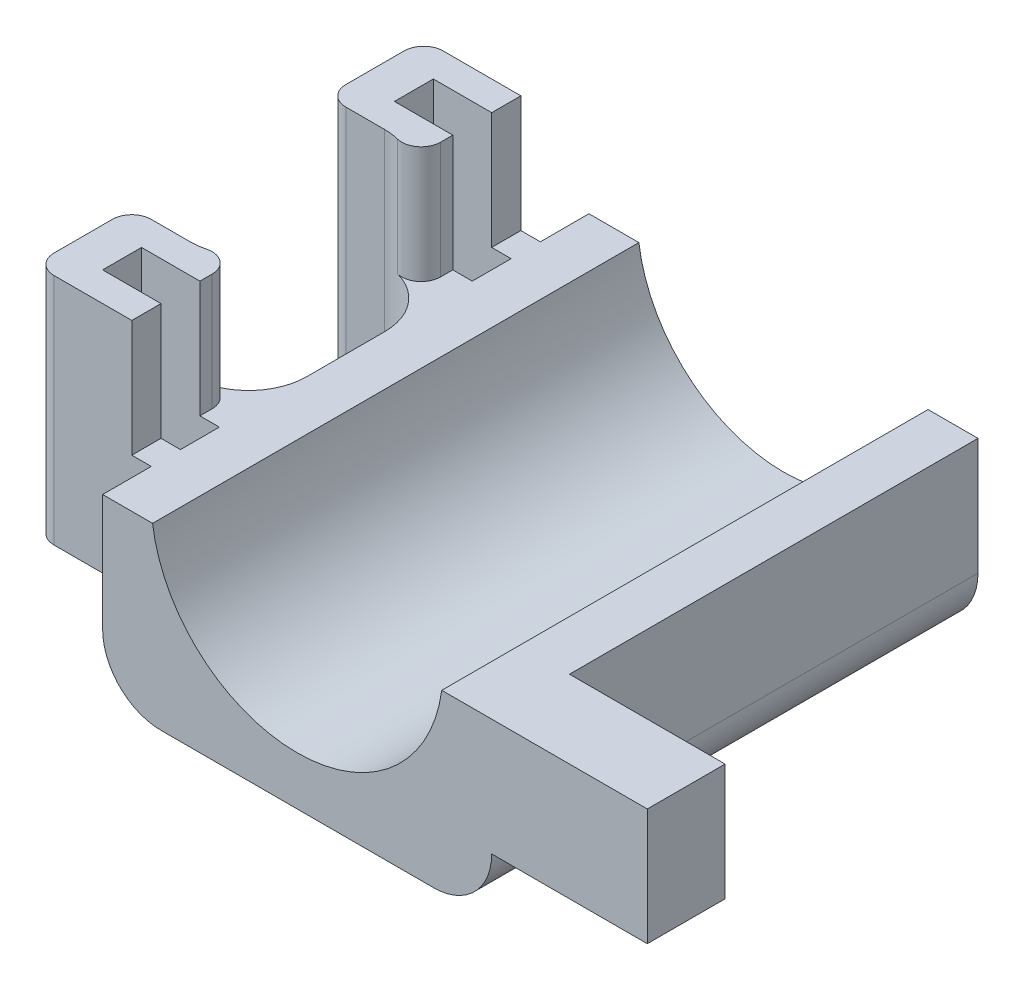
SolidWorks part; units mm, degrees
ref_plane "Plano frontal" through (0, 0, 0) normal (0, 0, 1) x (1, 0, 0)
ref_plane "Plano superior" through (0, 0, 0) normal (0, 1, 0) x (1, 0, 0)
ref_plane "Plano direito" through (0, 0, 0) normal (1, 0, 0) x (0, 0, -1)
sketch "Esboço1" plane through (0, 0, 0) normal (0, 1, 0) x (1, 0, 0)
  line L1 (-10, 12.5) -> (10, 12.5)
  line L2 (-10, 12.5) -> (-10, -12.5)
  line L3 (-10, -12.5) -> (10, -12.5)
  line L4 (10, 12.5) -> (10, -12.5)
  line L5 (-10, 12.5) -> (10, -12.5) construction
  line L6 (-10, -12.5) -> (10, 12.5) construction
  point P0 (0, 0)
  dimension "D1" = 20
  dimension "D2" = 25
extrude "Ressalto-extrusão1" add sketch "Esboço1" along normal blind 9
sketch "Esboço2" plane through (0, 0, 12.5) normal (0, 0, 1) x (1, 0, 0)
  line L0 (-10, 9) -> (10, 9) construction
  circle A0 centre (0, 10) radius 7.5
  dimension "D2" = 15
  dimension "D1" = 1
extrude "Corte-extrusão1" cut sketch "Esboço2" against normal through all
fillet "Filete1" radius 3 2 edges at (10, 0, 0) (-10, 0, 0)
sketch "Esboço3" plane through (0, 9, 0) normal (0, 1, 0) x (1, 0, 0)
  line L0 (-16, 10) -> (-10, 5) construction
  line L5 (-10, 12.5) -> (-10, -12.5) construction
  line L10 (-9.5, -5) -> (-16.5, -10) construction
  line L15 (-16, 10) -> (-10, 10)
  line L16 (-16, 10) -> (-16, 5)
  line L17 (-16, 5) -> (-10, 5)
  line L18 (-10, 10) -> (-10, 8.5)
  line L19 (-13, 7.5) -> (-13, -7.5) construction
  line L20 (-10, 6.5) -> (-10, 5)
  line L21 (-14, 8.5) -> (-10, 8.5)
  line L22 (-14, 8.5) -> (-14, 6.5)
  line L23 (-14, 6.5) -> (-10, 6.5)
  line L25 (0, 0) -> (-10, 0) construction
  line L26 (-14, -6.5) -> (-10, -6.5)
  line L27 (-14, -8.5) -> (-14, -6.5)
  line L28 (-14, -8.5) -> (-10, -8.5)
  line L29 (-10, -6.5) -> (-10, -5)
  line L30 (-10, -10) -> (-10, -8.5)
  line L31 (-16, -5) -> (-10, -5)
  line L32 (-16, -10) -> (-16, -5)
  line L33 (-16, -10) -> (-10, -10)
  point P14 (-13, 0)
  point P22 (-14, 7.5)
  dimension "D1" = 15
  dimension "D2" = 6
  dimension "D3" = 5
  dimension "D4" = 4
  dimension "D5" = 2
extrude "Ressalto-extrusão2" add sketch "Esboço3" against normal blind 6
sketch "Esboço4" plane through (0, 9, 0) normal (0, 1, 0) x (1, 0, 0)
  line L0 (-16, -10) -> (-16, -5)
  line L1 (-16, -5) -> (-11, -5)
  line L2 (-10, -5) -> (-16, -5) construction
  line L3 (-11, -5) -> (-11, -6.5)
  line L4 (-14, -6.5) -> (-10, -6.5) construction
  line L5 (-11, -6.5) -> (-14, -6.5)
  line L6 (-14, -6.5) -> (-14, -8.5)
  line L7 (-14, -8.5) -> (-11, -8.5)
  line L8 (-10, -8.5) -> (-14, -8.5) construction
  line L9 (-11, -8.5) -> (-11, -10)
  line L10 (-16, -10) -> (-10, -10) construction
  line L11 (-11, -10) -> (-16, -10)
  line L12 (-10, 5) -> (-10, -5) construction
  line L13 (0, 0) -> (-10, 0) construction
  line L14 (-11, 10) -> (-16, 10)
  line L15 (-11, 8.5) -> (-11, 10)
  line L16 (-14, 8.5) -> (-11, 8.5)
  line L17 (-14, 6.5) -> (-14, 8.5)
  line L18 (-11, 6.5) -> (-14, 6.5)
  line L19 (-11, 5) -> (-11, 6.5)
  line L20 (-16, 5) -> (-11, 5)
  line L21 (-16, 10) -> (-16, 5)
  dimension "D1" = 1
extrude "Ressalto-extrusão3" add sketch "Esboço4" along normal blind 6
fillet "Filete3" radius 1 4 edges at (-16, 9, -10) (-16, 9, -5) (-16, 9, 5) (-16, 9, 10)
fillet "Filete5" radius 3 2 edges at (-10, 6, -5) (-10, 6, 5)
fillet "Filete6" radius 1 2 edges at (-11, 12, -4.2361) (-11, 12, 4.2361)
sketch "Esboço5" plane through (10, 0, 0) normal (1, 0, 0) x (0, 0, -1)
  line L0 (-12.5, 3) -> (12.5, 3) construction
  line L1 (-12.5, 9) -> (-8.5, 9)
  line L2 (-12.5, 9) -> (-12.5, 3)
  line L3 (-12.5, 3) -> (-8.5, 3)
  line L4 (-8.5, 9) -> (-8.5, 3)
  dimension "D1" = 4
extrude "Ressalto-extrusão4" add sketch "Esboço5" along normal blind 8
